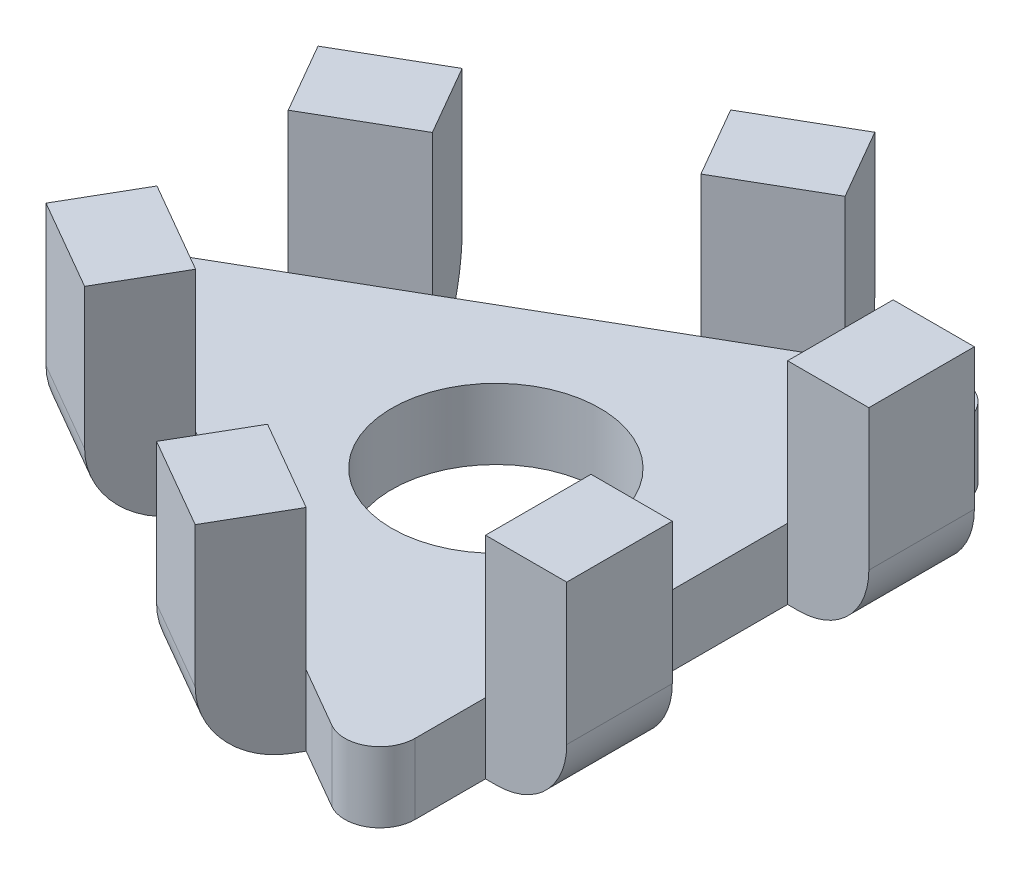
SolidWorks part; units mm, degrees
material "PLA"
ref_plane "Front" through (0, 0, 0) normal (0, 0, 1) x (1, 0, 0)
ref_plane "Top" through (0, 0, 0) normal (0, 1, 0) x (1, 0, 0)
ref_plane "Right" through (0, 0, 0) normal (1, 0, 0) x (0, 0, -1)
sketch "Sketch2" plane through (0, 0, 0) normal (0, 1, 0) x (0, 0, -1)
  line L0 (0, 0) -> (0, 50) construction
  line L1 (0, 0) -> (-43.3013, -25) construction
  line L2 (-43.3013, -20) -> (-38.3013, -11.3397)
  line L3 (4.3301, 47.5) -> (9.3301, 38.8397)
  line L4 (38.9711, -27.5) -> (28.9711, -27.5)
  line L5 (0, 0) -> (-23.8157, 13.75) construction
  line L9 (-38.3013, -11.3397) -> (-48.3013, -5.5662)
  line L10 (-30.8013, 1.6506) -> (-40.8013, 7.4241)
  line L11 (-48.3013, -5.5662) -> (-40.8013, 7.4241)
  line L12 (-16.8301, 25.8494) -> (-26.8301, 31.6229)
  line L13 (-19.3301, 44.6132) -> (-26.8301, 31.6229)
  line L14 (-9.3301, 38.8397) -> (-19.3301, 44.6132)
  line L17 (9.3301, 38.8397) -> (19.3301, 44.6132)
  line L18 (19.3301, 44.6132) -> (26.8301, 31.6229)
  line L19 (16.8301, 25.8494) -> (26.8301, 31.6229)
  line L20 (30.8013, 1.6506) -> (40.8013, 7.4241)
  line L21 (48.3013, -5.5662) -> (40.8013, 7.4241)
  line L22 (38.3013, -11.3397) -> (48.3013, -5.5662)
  line L25 (28.9711, -27.5) -> (28.9711, -39.047)
  line L26 (28.9711, -39.047) -> (13.9711, -39.047)
  line L27 (13.9711, -27.5) -> (13.9711, -39.047)
  line L28 (-28.9711, -27.5) -> (-28.9711, -39.047)
  line L29 (-28.9711, -39.047) -> (-13.9711, -39.047)
  line L30 (-13.9711, -27.5) -> (-13.9711, -39.047)
  line L32 (-30.8013, 1.6506) -> (-16.8301, 25.8494)
  line L33 (-9.3301, 38.8397) -> (-4.3301, 47.5)
  line L34 (16.8301, 25.8494) -> (30.8013, 1.6506)
  line L35 (38.3013, -11.3397) -> (43.3013, -20)
  line L36 (13.9711, -27.5) -> (-13.9711, -27.5)
  line L37 (-28.9711, -27.5) -> (-38.9711, -27.5)
  line L38 (-38.3013, -11.3397) -> (-30.8013, 1.6506)
  line L39 (-9.3301, 38.8397) -> (-16.8301, 25.8494)
  line L40 (9.3301, 38.8397) -> (16.8301, 25.8494)
  line L41 (38.3013, -11.3397) -> (30.8013, 1.6506)
  line L42 (28.9711, -27.5) -> (13.9711, -27.5)
  line L43 (-28.9711, -27.5) -> (-13.9711, -27.5)
  arc A0 (-43.3013, -20) -> (-38.9711, -27.5) centre (-38.9711, -22.5) ccw
  arc A1 (43.3013, -20) -> (38.9711, -27.5) centre (38.9711, -22.5) cw
  arc A2 (4.3301, 47.5) -> (-4.3301, 47.5) centre (0, 45) ccw
  circle A3 centre (-38.9711, -22.5) radius 5 construction
  circle A4 centre (0, 0) radius 14.7988
  dimension "D4" = 10
  dimension "D6" = 10
  dimension "D1" = 29.5977
  dimension "D3" = 50
  dimension "D7" = 15
  dimension "D8" = 10
extrude "Boss-Extrude1" add sketch "Sketch2" along normal blind 10 contours L3 A2 L33 L39 L32 L38 L2 A0 L37 L43 L36 L42 L4 A1 L35 L41 L34 L40 region at (16.256, 0, 39.7861)
extrude "Boss-Extrude3" add sketch "Sketch2<7>" along normal blind 30 contours L41 L22 L21 L20 | L25 L42 L27 L26 | L43 L28 L29 L30 | L9 L38 L10 L11 | L39 L14 L13 L12 | L17 L40 L19 L18 region at (1.9578, 0, 39.5513) region at (33.2735, 0, 21.4711) region at (-35.2313, 0, 18.0801) region at (33.2735, 0, -21.4711) region at (-35.2313, 0, -18.0801) region at (1.9578, 0, -39.5513)
sketch "Sketch2<7>" plane through (0, 0, 0) normal (0, 1, 0) x (0, 0, -1) same geometry as "Sketch2"
fillet "Fillet1" radius 10 6 edges at (39.047, 0, -21.4711) (39.047, 0, 21.4711) (-0.9289, 0, 44.5513) (-38.1181, 0, 23.0801) (-38.1181, 0, -23.0801) (-0.9289, 0, -44.5513)
sketch "Sketch8" plane through (-19.5235, 0, 33.8157) normal (-0.5, 0, 0.866) x (0.866, 0, 0.5)
  line L1 (-21.4711, 30) -> (-21.4331, 20) construction
  line L2 (-28.9711, 30) -> (-13.9711, 30) construction
  line L3 (-28.9711, 20) -> (-21.4331, 20) construction
  line L4 (-28.9711, 30) -> (-28.9711, 10) construction
  point P0 (-21.4331, 20)
  point P6 (0, 0)
  point P9 (0, 0)
  point P10 (0, 0)
  point P11 (0, 0)
